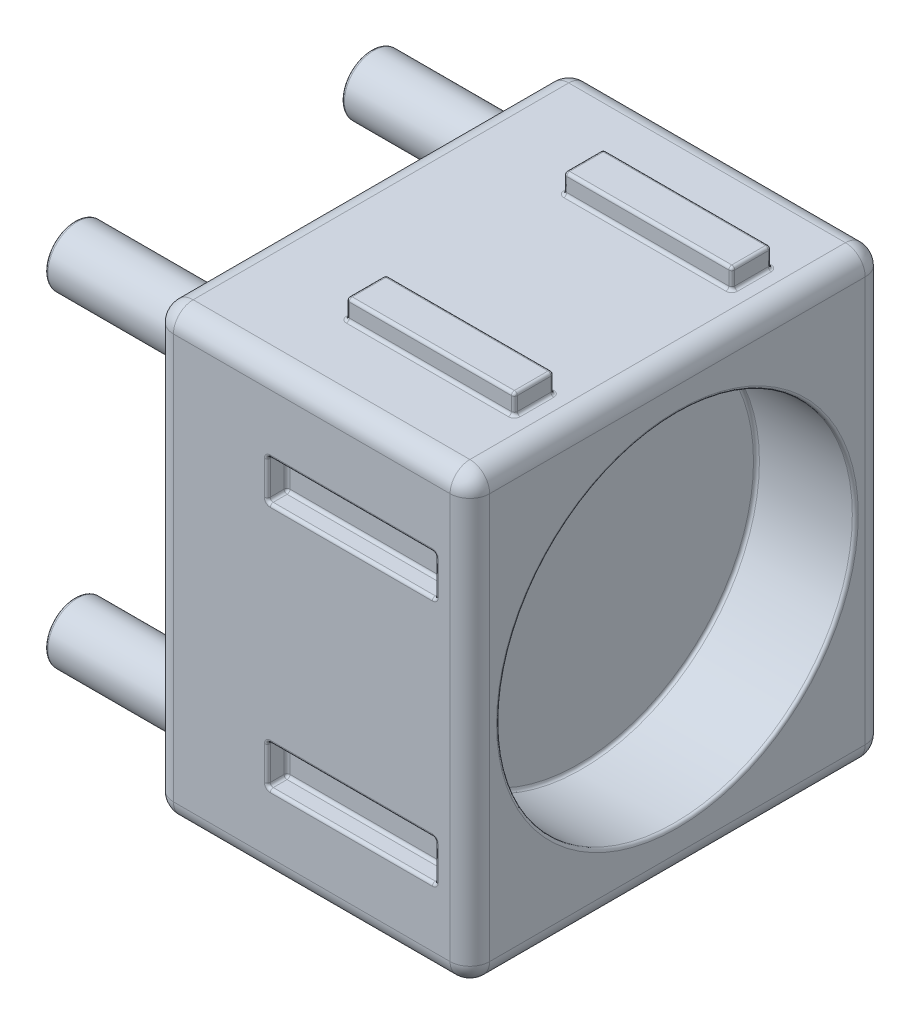
SolidWorks part; units mm, degrees
ref_plane "Front Plane" through (0, 0, 0) normal (0, 0, 1) x (1, 0, 0)
ref_plane "Top Plane" through (0, 0, 0) normal (0, 1, 0) x (1, 0, 0)
ref_plane "Right Plane" through (0, 0, 0) normal (1, 0, 0) x (0, 0, -1)
sketch "Sketch1" plane through (0, 0, 0) normal (0, 1, 0) x (1, 0, 0)
  line L1 (-8, 10.5) -> (8, 10.5)
  line L2 (-8, 10.5) -> (-8, -10.5)
  line L3 (-8, -10.5) -> (8, -10.5)
  line L4 (8, 10.5) -> (8, -10.5)
  line L5 (-8, 10.5) -> (8, -10.5) construction
  line L6 (-8, -10.5) -> (8, 10.5) construction
  point P0 (0, 0)
  dimension "D1" = 21
  dimension "D2" = 16
extrude "Boss-Extrude1" add sketch "Sketch1" along normal blind 22.5
sketch "Sketch2" plane through (8, 0, 0) normal (1, 0, 0) x (0, 0, -1)
  line L0 (0, 22.5) -> (0, 0) construction
  line L1 (-10.5, 22.5) -> (10.5, 22.5) construction
  line L2 (-10.5, 0) -> (10.5, 0) construction
  line L3 (-10.5, 11.25) -> (10.5, 11.25) construction
  line L4 (-10.5, 22.5) -> (-10.5, 0) construction
  line L5 (10.5, 22.5) -> (10.5, 0) construction
  circle A0 centre (0, 11.25) radius 9
  dimension "D1" = 18
extrude "Cut-Extrude1" cut sketch "Sketch2" against normal blind 5
sketch "Sketch3" plane through (-8, 0, 0) normal (-1, 0, 0) x (0, 0, 1)
  line L0 (-10.5, 22.5) -> (10.5, 22.5) construction
  line L1 (10.5, 22.5) -> (10.5, 0) construction
  line L2 (0, 0) -> (0, 22.5) construction
  line L3 (-10.5, 0) -> (10.5, 0) construction
  line L4 (10.5, 11.25) -> (-10.5, 11.25) construction
  line L5 (-10.5, 22.5) -> (-10.5, 0) construction
  circle A0 centre (7.5, 19.5) radius 1.5
  circle A1 centre (7.5, 3) radius 1.5
  circle A2 centre (-7.5, 19.5) radius 1.5
  circle A3 centre (-7.5, 3) radius 1.5
  dimension "D1" = 3
  dimension "D2" = 3
  dimension "D3" = 3
extrude "Boss-Extrude2" add sketch "Sketch3" along normal blind 7
sketch "Sketch4" plane through (-8, 0, 0) normal (-1, 0, 0) x (0, 0, 1)
  line L0 (10.5, 11.25) -> (-10.5, 11.25) construction
  line L1 (10.5, 22.5) -> (10.5, 0) construction
  line L2 (-10.5, 22.5) -> (-10.5, 0) construction
  line L3 (0, 0) -> (0, 22.5) construction
  line L4 (-10.5, 0) -> (10.5, 0) construction
  line L5 (-10.5, 22.5) -> (10.5, 22.5) construction
  circle A0 centre (0, 11.25) radius 1.5
  dimension "D1" = 3
extrude "Boss-Extrude3" add sketch "Sketch4" along normal blind 5
fillet "Fillet3" radius 1 12 edges at (-8, 11.25, -10.5) (0, 22.5, -10.5) (0, 0, -10.5) (-8, 0, 0) (0, 22.5, 10.5) (-8, 22.5, 0) (-8, 11.25, 10.5) (0, 0, 10.5) (8, 11.25, 10.5) (8, 0, 0) (8, 11.25, -10.5) (8, 22.5, 0)
sketch "Sketch5" plane through (0, 0, 0) normal (0, -1, 0) x (-1, 0, 0)
  line L0 (7, 9.5) -> (-7, 9.5) construction
  line L1 (6.25, 6.5) -> (-2.25, 6.5)
  line L2 (6.25, 6.5) -> (6.25, 4.5)
  line L3 (6.25, 4.5) -> (-2.25, 4.5)
  line L4 (-2.25, 6.5) -> (-2.25, 4.5)
  line L5 (-8, -9.5) -> (-8, 9.5) construction
  line L7 (-8, 0) -> (7, 0) construction
  line L8 (7, -9.5) -> (7, 9.5) construction
  line L9 (6.25, -6.5) -> (6.25, -4.5)
  line L10 (-2.25, -6.5) -> (-2.25, -4.5)
  line L11 (6.25, -6.5) -> (-2.25, -6.5)
  line L12 (6.25, -4.5) -> (-2.25, -4.5)
  dimension "D1" = 3
  dimension "D2" = 0.75
  dimension "D3" = 2
  dimension "D4" = 8.5
extrude "Cut-Extrude2" cut sketch "Sketch5" against normal blind 1
sketch "Sketch6" plane through (0, 0, 10.5) normal (0, 0, 1) x (1, 0, 0)
  line L0 (-7, 1) -> (7, 1) construction
  line L1 (-2.25, 4) -> (6.25, 4)
  line L2 (-2.25, 4) -> (-2.25, 6)
  line L3 (-2.25, 6) -> (6.25, 6)
  line L4 (6.25, 4) -> (6.25, 6)
  line L5 (7, 1) -> (7, 21.5) construction
  line L6 (7, 11.25) -> (-7, 11.25) construction
  line L7 (-7, 21.5) -> (-7, 1) construction
  line L8 (-2.25, 18.5) -> (-2.25, 16.5)
  line L9 (6.25, 18.5) -> (6.25, 16.5)
  line L10 (-2.25, 18.5) -> (6.25, 18.5)
  line L11 (-2.25, 16.5) -> (6.25, 16.5)
  dimension "D1" = 3
  dimension "D2" = 0.75
  dimension "D3" = 8.5
  dimension "D4" = 2
extrude "Cut-Extrude3" cut sketch "Sketch6" against normal blind 1
sketch "Sketch7" plane through (0, 22.5, 0) normal (0, 1, 0) x (1, 0, 0)
  line L0 (-7, -9.5) -> (7, -9.5) construction
  line L1 (-2.25, -6.5) -> (6.25, -6.5)
  line L2 (-2.25, -6.5) -> (-2.25, -4.5)
  line L3 (-2.25, -4.5) -> (6.25, -4.5)
  line L4 (6.25, -6.5) -> (6.25, -4.5)
  line L5 (7, -9.5) -> (7, 9.5) construction
  line L6 (-7, 0) -> (7, 0) construction
  line L7 (-7, 9.5) -> (-7, -9.5) construction
  line L8 (6.25, 6.5) -> (6.25, 4.5)
  line L9 (-2.25, 6.5) -> (-2.25, 4.5)
  line L10 (-2.25, 6.5) -> (6.25, 6.5)
  line L11 (-2.25, 4.5) -> (6.25, 4.5)
  dimension "D1" = 3
  dimension "D2" = 0.75
  dimension "D3" = 8.5
  dimension "D4" = 2
extrude "Boss-Extrude4" add sketch "Sketch7" along normal blind 1
sketch "Sketch8" plane through (0, 0, -10.5) normal (0, 0, -1) x (-1, 0, 0)
  line L0 (7, 21.5) -> (-7, 21.5) construction
  line L1 (2.25, 18.5) -> (-6.25, 18.5)
  line L2 (2.25, 18.5) -> (2.25, 16.5)
  line L3 (2.25, 16.5) -> (-6.25, 16.5)
  line L4 (-6.25, 18.5) -> (-6.25, 16.5)
  line L5 (-7, 21.5) -> (-7, 1) construction
  line L6 (7, 11.25) -> (-7, 11.25) construction
  line L7 (7, 1) -> (7, 21.5) construction
  line L8 (-6.25, 4) -> (-6.25, 6)
  line L9 (2.25, 4) -> (-6.25, 4)
  line L10 (2.25, 4) -> (2.25, 6)
  line L11 (2.25, 6) -> (-6.25, 6)
  dimension "D1" = 3
  dimension "D2" = 0.75
  dimension "D3" = 8.5
  dimension "D4" = 2
extrude "Boss-Extrude5" add sketch "Sketch8" along normal blind 1
fillet "Fillet4" radius 0.15 96 edges at (-2.25, 17.5, 9.5) (-2.25, 17.5, 10.5) (2, 18.5, 9.5) (-2.25, 18.5, 10) (2, 18.5, 10.5) (6.25, 17.5, 9.5) (6.25, 18.5, 10) (6.25, 17.5, 10.5) (-2.25, 16.5, 10) (2, 16.5, 9.5) (6.25, 16.5, 10) (2, 16.5, 10.5) (2, 4, 9.5) (2, 4, 10.5) (6.25, 4, 10) (6.25, 5, 9.5) (6.25, 5, 10.5) (6.25, 6, 10) (2, 6, 9.5) (2, 6, 10.5) (-2.25, 6, 10) (-2.25, 5, 9.5) (-2.25, 4, 10) (-2.25, 5, 10.5) (2.25, 1, 5.5) (2.25, 0, 5.5) (2.25, 0.5, 6.5) (-2, 1, 6.5) (-2, 0, 6.5) (-2, 1, 4.5) (2.25, 0.5, 4.5) (-2, 0, 4.5) (-6.25, 0.5, 6.5) (-6.25, 1, 5.5) (-6.25, 0.5, 4.5) (-6.25, 0, 5.5) (-6.25, 1, -5.5) (-6.25, 0, -5.5) (-6.25, 0.5, -6.5) (-2, 1, -6.5) (-2, 0, -6.5) (2.25, 0.5, -6.5) (2.25, 1, -5.5) (2.25, 0, -5.5) (2.25, 0.5, -4.5) (-2, 1, -4.5) (-6.25, 0.5, -4.5) (-2, 0, -4.5) (-2.25, 5, -11.5) (-2.25, 5, -10.5) (-2.25, 6, -11) (2, 6, -11.5) (2, 6, -10.5) (2, 4, -11.5) (-2.25, 4, -11) (2, 4, -10.5) (6.25, 6, -11) (6.25, 5, -11.5) (6.25, 4, -11) (6.25, 5, -10.5) (6.25, 17.5, -11.5) (6.25, 17.5, -10.5) (6.25, 16.5, -11) (2, 16.5, -11.5) (2, 16.5, -10.5) (-2.25, 16.5, -11) (-2.25, 17.5, -11.5) (-2.25, 17.5, -10.5) (-2.25, 18.5, -11) (2, 18.5, -11.5) (6.25, 18.5, -11) (2, 18.5, -10.5) (-2.25, 23.5, -5.5) (-2.25, 22.5, -5.5) (-2.25, 23, -4.5) (2, 23.5, -4.5) (2, 22.5, -4.5) (2, 23.5, -6.5) (-2.25, 23, -6.5) (2, 22.5, -6.5) (6.25, 23, -4.5) (6.25, 23.5, -5.5) (6.25, 23, -6.5) (6.25, 22.5, -5.5) (2, 23.5, 4.5) (2, 22.5, 4.5) (6.25, 23.5, 5.5) (6.25, 23, 4.5) (6.25, 22.5, 5.5) (2, 23.5, 6.5) (6.25, 23, 6.5) (2, 22.5, 6.5) (-2.25, 23, 4.5) (-2.25, 23.5, 5.5) (-2.25, 23, 6.5) (-2.25, 22.5, 5.5)
fillet "Fillet5" radius 0.15 10 edges at (-8, 3, 6) (-15, 3, 6) (-8, 19.5, 6) (-15, 19.5, 9) (-8, 19.5, -9) (-15, 19.5, -9) (-8, 11.25, -1.5) (-13, 11.25, 1.5) (-8, 3, -9) (-15, 3, -6)
fillet "Fillet6" radius 0.15 2 edges at (8, 11.25, -9) (3, 11.25, -9)
